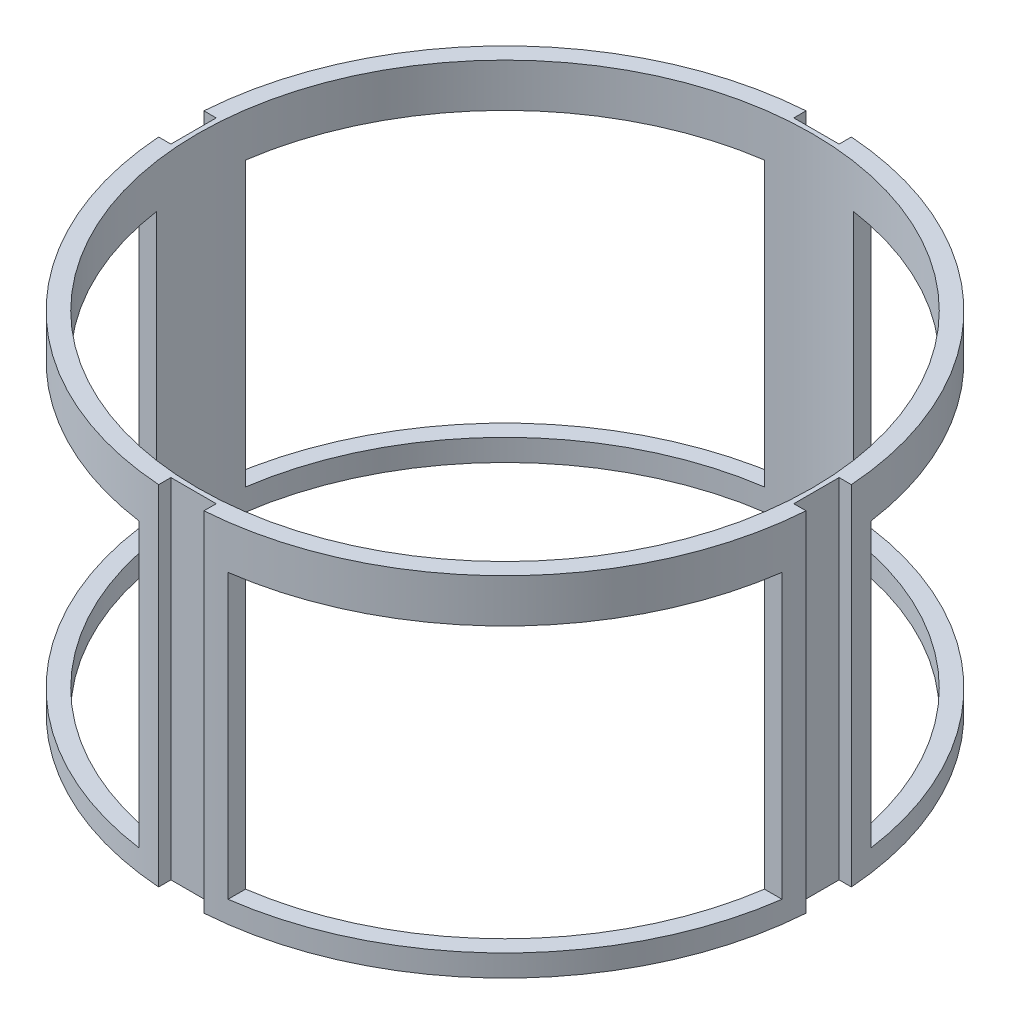
SolidWorks part; units mm, degrees
ref_plane "Front" through (0, 0, 0) normal (0, 0, 1) x (1, 0, 0)
ref_plane "Top" through (0, 0, 0) normal (0, 1, 0) x (1, 0, 0)
ref_plane "Right" through (0, 0, 0) normal (1, 0, 0) x (0, 0, -1)
sketch "Sketch1" plane through (0, 0, 0) normal (0, 1, 0) x (1, 0, 0)
  circle A0 centre (0, 0) radius 89.535
  circle A1 centre (0, 0) radius 94.615
  dimension "Inner Diameter" = 179.07
  dimension "Outer Diameter" = 189.23
extrude "Boss-Extrude1" add sketch "Sketch1" against normal blind 101.6
sketch "Sketch5" plane through (0, 0, 0) normal (0, 1, 0) x (1, 0, 0)
  line L0 (0, 114.2751) -> (0, -136.7211) construction
  line L1 (-124.857, 0) -> (116.4345, 0) construction
  line L2 (-6.604, 90.805) -> (6.604, 90.805)
  line L3 (6.604, 90.805) -> (6.604, 95.885)
  line L4 (6.604, 95.885) -> (-6.604, 95.885)
  line L5 (-6.604, 95.885) -> (-6.604, 90.805)
  line L6 (6.604, -95.885) -> (-6.604, -95.885)
  line L7 (6.604, -90.805) -> (6.604, -95.885)
  line L8 (-6.604, -90.805) -> (6.604, -90.805)
  line L9 (-6.604, -95.885) -> (-6.604, -90.805)
  line L10 (-90.805, 6.604) -> (-90.805, -6.604)
  line L11 (-90.805, -6.604) -> (-95.885, -6.604)
  line L12 (-95.885, -6.604) -> (-95.885, 6.604)
  line L13 (-95.885, 6.604) -> (-90.805, 6.604)
  line L14 (95.885, -6.604) -> (95.885, 6.604)
  line L15 (90.805, -6.604) -> (95.885, -6.604)
  line L16 (90.805, 6.604) -> (90.805, -6.604)
  line L17 (95.885, 6.604) -> (90.805, 6.604)
  dimension "D1" = 6.604
  dimension "D2" = 6.604
  dimension "D3" = 5.08
  dimension "D4" = 90.805
  dimension "D5" = 6.604
  dimension "D6" = 90.805
extrude "Cut-Extrude1" cut sketch "Sketch5" against normal blind 101.6
sketch "Sketch7" plane through (0, 0, 0) normal (0, 1, 0) x (1, 0, 0)
  line L0 (88.5929, -12.954) -> (93.724, -12.954)
  line L1 (12.954, -88.5929) -> (12.954, -93.724)
  line L2 (6.604, -94.3842) -> (6.604, -90.805) construction
  line L3 (90.805, -6.604) -> (94.3842, -6.604) construction
  arc A0 (88.5929, -12.954) -> (12.954, -88.5929) centre (0, 0) cw
  circle A1 centre (0, 0) radius 89.535 construction
  arc A2 (93.724, -12.954) -> (12.954, -93.724) centre (0, 0) cw
  arc A3 (6.604, -94.3842) -> (94.3842, -6.604) centre (0, 0) ccw construction
  point P15 (92.5946, -6.604)
  dimension "D3" = 94.615
  dimension "D4" = 89.535
  dimension "D1" = 6.35
  dimension "D2" = 6.35
extrude "Cut-Extrude2" cut sketch "Sketch7" against normal blind 82.55 from offset 12.7 offset against normal yes
pattern_circular "CirPattern1" count 4 over 360 about axis through (0, 0, 0) along (0, 1, 0) of "Cut-Extrude2"
equation "\"D4@Sketch5\"=(\"Inner Diameter\"/2)+((\"Outer Diameter\"-\"Inner Diameter\")/8)"
equation "\"D6@Sketch5\"=(\"Inner Diameter\"/2)+((\"Outer Diameter\"-\"Inner Diameter\")/8)"
equation "\"D1@Cut-Extrude1\"=\"Fin Length\""
equation "\"D3@Sketch7\"=\"Outer Diameter\"/2"
equation "\"D4@Sketch7\"=\"Inner Diameter\"/2"
